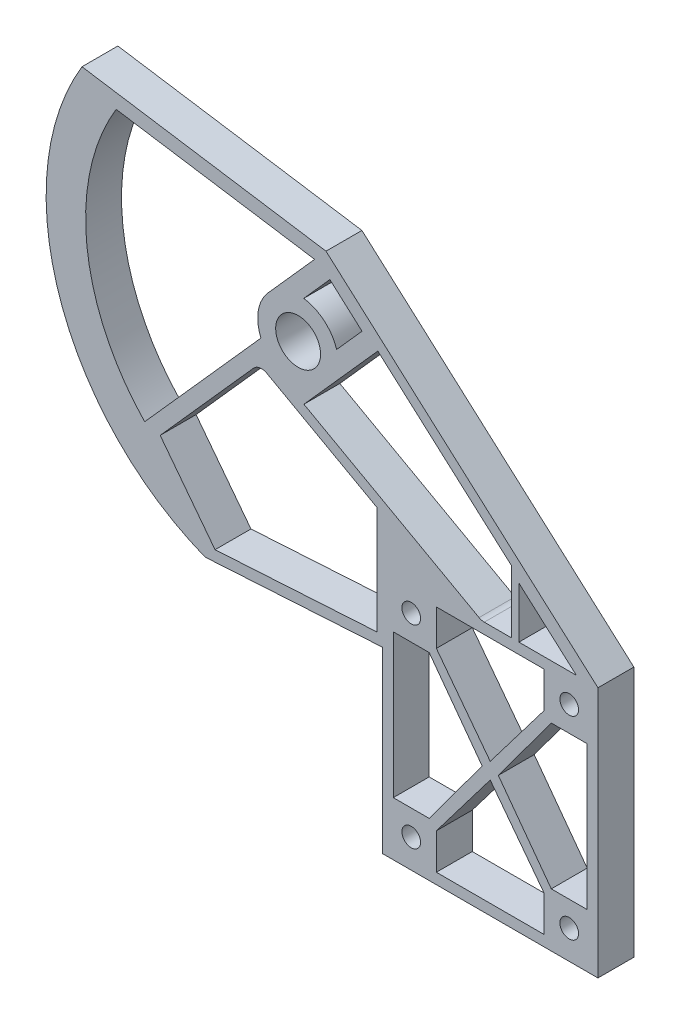
SolidWorks part; units mm, degrees
material "Magnesium Alloy"
ref_plane "Front Plane" through (0, 0, 0) normal (0, 0, 1) x (1, 0, 0)
ref_plane "Top Plane" through (0, 0, 0) normal (0, 1, 0) x (1, 0, 0)
ref_plane "Right Plane" through (0, 0, 0) normal (1, 0, 0) x (0, 0, -1)
sketch "Sketch1" plane through (0, 0, 0) normal (0, 0, 1) x (1, 0, 0)
  line L3 (22.6053, 67.0523) -> (98.8053, 67.0523)
  line L4 (98.8053, 155.9523) -> (98.8053, 67.0523)
  line L7 (60.7053, 155.2939) -> (60.7053, 67.0523) construction
  line L8 (184.9087, 111.5023) -> (-17.2677, 111.5023) construction
  line L11 (98.8053, 155.9523) -> (-49.1612, 287.7)
  line L14 (22.6053, 67.0523) -> (22.6053, 130.2741)
  line L15 (-40.152, 126.5029) -> (22.6053, 130.2741)
  arc A1 (-40.152, 126.5029) -> (-49.1612, 287.7) centre (-7.475, 209.1795) cw
  dimension "D3" = 88.9
  dimension "D1" = 88.9
  dimension "D7" = 44.45
  dimension "D8" = 38.1
  dimension "D9" = 76.2
extrude "Boss-Extrude1" add sketch "Sketch1" along normal blind 12.7
sketch "Sketch2" plane through (0, 0, 12.7) normal (0, 0, 1) x (1, 0, 0)
  line L2 (22.6053, 67.0523) -> (98.8053, 67.0523) construction
  line L3 (22.6053, 130.2741) -> (22.6053, 67.0523) construction
  circle A0 centre (-7.2397, 209.0383) radius 7.9375
  dimension "D2" = 15.875
  dimension "D1" = 141.986
  dimension "D3" = 29.845
extrude "Cut-Extrude1" cut sketch "Sketch2" against normal blind 25.4
ref_axis "Axis1" through (-7.2397, 209.0383, 0) along (0, 0, 1)
ref_axis "Axis2" through (-7.475, 209.1795, 12.7) along (0, 0, -1)
sketch "Sketch3" plane through (0, 0, 12.7) normal (0, 0, 1) x (1, 0, 0)
  line L0 (41.6553, 70.8623) -> (41.6553, 83.5623)
  line L1 (41.6553, 83.5623) -> (60.7053, 108.6448)
  line L2 (60.7053, 108.6448) -> (79.7553, 83.5623)
  line L3 (79.7553, 83.5623) -> (79.7553, 70.8623)
  line L4 (79.7553, 70.8623) -> (41.6553, 70.8623)
  line L5 (26.4153, 86.1023) -> (39.1153, 86.1023)
  line L6 (39.1153, 86.1023) -> (57.8478, 111.5023)
  line L7 (57.8478, 111.5023) -> (39.1153, 136.9023)
  line L8 (39.1153, 136.9023) -> (26.4153, 136.9023)
  line L9 (26.4153, 136.9023) -> (26.4153, 86.1023)
  line L10 (94.9953, 86.1023) -> (82.2953, 86.1023)
  line L11 (82.2953, 86.1023) -> (63.5628, 111.5023)
  line L12 (63.5628, 111.5023) -> (82.2953, 136.9023)
  line L13 (82.2953, 136.9023) -> (94.9953, 136.9023)
  line L14 (94.9953, 136.9023) -> (94.9953, 86.1023)
  line L15 (41.6553, 152.1423) -> (41.6553, 139.4423)
  line L16 (41.6553, 139.4423) -> (60.7053, 114.3598)
  line L17 (60.7053, 114.3598) -> (79.7553, 139.4423)
  line L18 (79.7553, 139.4423) -> (79.7553, 152.1423)
  line L19 (79.7553, 152.1423) -> (41.6553, 152.1423)
  line L20 (22.6053, 67.0523) -> (98.8053, 67.0523) construction
  line L21 (98.8053, 67.0523) -> (98.8053, 155.9523) construction
  line L22 (22.6053, 130.2741) -> (22.6053, 67.0523) construction
  dimension "D1" = 3.81
  dimension "D2" = 3.81
  dimension "D3" = 3.81
  dimension "D4" = 3.81
  dimension "D5" = 19.05
  dimension "D6" = 19.05
  dimension "D7" = 19.05
  dimension "D8" = 19.05
  dimension "D10" = 19.05
  dimension "D11" = 12.7
  dimension "D12" = 12.7
  dimension "D13" = 12.7
  dimension "D14" = 12.7
  dimension "D16" = 5.715
  dimension "D17" = 5.715
extrude "Cut-Extrude2" cut sketch "Sketch3" against normal blind 15.24
sketch "Sketch5" plane through (0, 0, 12.7) normal (0, 0, 1) x (1, 0, 0)
  line L2 (-0.7594, 237.8017) -> (-42.8182, 275.2504)
  line L3 (98.8053, 155.9523) -> (-49.1612, 287.7) construction
  line L4 (-36.6202, 130.532) -> (-56.0379, 155.8518)
  line L5 (-17.9104, 218.5393) -> (-0.7594, 237.8017)
  line L6 (-5.268, 223.1891) -> (3.9831, 233.579)
  line L7 (3.9831, 233.579) -> (15.3651, 223.4446)
  line L8 (15.3651, 223.4446) -> (6.3804, 213.3538)
  line L12 (-61.5192, 157.2784) -> (-20.3953, 203.4649)
  line L14 (20.7003, 172.0765) -> (-20.9942, 195.2095)
  line L15 (-20.9942, 195.2095) -> (-56.0379, 155.8518)
  line L17 (26.4153, 136.9023) -> (26.4153, 86.1023) construction
  line L18 (-36.6202, 130.532) -> (20.7003, 133.9765)
  line L19 (20.7003, 133.9765) -> (20.7003, 172.0765)
  line L20 (-40.152, 126.5029) -> (22.6053, 130.2741) construction
  arc A0 (-61.5192, 157.2784) -> (-42.8182, 275.2504) centre (-7.475, 209.1795) cw
  arc A1 (-49.1612, 287.7) -> (-40.152, 126.5029) centre (-7.475, 209.1795) ccw construction
  arc A2 (-20.3953, 203.4649) -> (-17.9104, 218.5393) centre (-7.2397, 209.0383) cw
  circle A3 centre (-7.2397, 209.0383) radius 7.9375 construction
  arc A4 (-5.268, 223.1891) -> (6.3804, 213.3538) centre (-7.2397, 209.0383) cw
  dimension "D1" = 13.97
  dimension "D4" = 6.35
  dimension "D6" = 6.35
  dimension "D2" = 5.08
  dimension "D3" = 90
  dimension "D5" = 6.35
  dimension "D7" = 15.24
  dimension "D8" = 5.08
  dimension "D9" = 38.1
  dimension "D10" = 13.97
  dimension "D12" = 5.715
  dimension "D13" = 3.81
extrude "Cut-Extrude4" cut sketch "Sketch5" against normal blind 12.7 contours A2 L5 L2 A0 | L15 L4 L18 L19 L14 | L12 A2 L5 L2 A0 | L8 A4 L6 L7 region at (-48.435, 220.0414, 12.7)
sketch "Sketch4" plane through (0, 0, 12.7) normal (0, 0, 1) x (1, 0, 0)
  line L3 (57.6155, 155.9523) -> (-5.1971, 190.802)
  line L4 (-5.1971, 190.802) -> (20.9522, 220.1704)
  line L15 (20.7003, 172.0765) -> (-20.9942, 195.2095) construction
  line L16 (15.3651, 223.4446) -> (6.3804, 213.3538) construction
  line L18 (91.166, 155.9523) -> (70.846, 155.9523)
  line L19 (70.846, 155.9523) -> (70.846, 174.045)
  line L20 (70.846, 174.045) -> (91.166, 155.9523)
  line L21 (98.8053, 155.9523) -> (-49.1612, 287.7) construction
  line L22 (79.7553, 152.1423) -> (41.6553, 152.1423) construction
  line L23 (68.306, 155.9523) -> (68.306, 178.007)
  line L24 (68.306, 178.007) -> (20.9522, 220.1704)
  line L26 (57.6155, 155.9523) -> (68.306, 155.9523)
  dimension "D1" = 3.81
  dimension "D2" = 5.08
  dimension "D3" = 20.32
  dimension "D4" = 3.81
  dimension "D5" = 2.54
  dimension "D6" = 6.35
  dimension "D8" = 3.81
extrude "Cut-Extrude3" cut sketch "Sketch4" against normal blind 12.7
sketch "Sketch6" plane through (0, 0, 12.7) normal (0, 0, 1) x (1, 0, 0)
  line L0 (-45.205, 275.6751) -> (-52.1749, 281.881)
  line L1 (-80.3549, 164.771) -> (-74.1405, 171.7505)
  line L3 (98.8053, 155.9523) -> (-49.1612, 287.7) construction
  line L4 (-61.5192, 157.2784) -> (-20.3953, 203.4649) construction
  arc A0 (-45.205, 275.6751) -> (-74.1405, 171.7505) centre (-7.475, 209.1795) ccw
  arc A1 (-52.1749, 281.881) -> (-80.3549, 164.771) centre (-7.475, 209.1795) ccw
  dimension "D1" = 8.89
  dimension "D2" = 76.454
  dimension "D3" = 6.35
  dimension "D4" = 19.05
extrude "Cut-Extrude5" [suppressed] cut sketch "Sketch6" against normal blind 3.81
fillet "Fillet4" radius 3.81 2 edges at (-20.9942, 195.2095, 6.35) (57.6155, 155.9523, 6.35)
sketch "Sketch10" plane through (0, 0, 12.7) normal (0, 0, 1) x (1, 0, 0)
  line L0 (22.6053, 67.0523) -> (98.8053, 67.0523) construction
  line L1 (98.8053, 67.0523) -> (98.8053, 155.9523) construction
  line L2 (22.6053, 130.2741) -> (22.6053, 67.0523) construction
  circle A0 centre (32.7653, 77.2123) radius 3.302
  circle A1 centre (32.7653, 145.7923) radius 3.302
  circle A2 centre (88.6453, 145.7923) radius 3.302
  circle A3 centre (88.6453, 77.2123) radius 3.302
  dimension "D1" = 6.604
  dimension "D2" = 10.16
  dimension "D3" = 10.16
  dimension "D4" = 10.16
  dimension "D5" = 10.16
extrude "Cut-Extrude8" cut sketch "Sketch10" against normal up to next
sketch "Sketch11" plane through (0, 0, 12.7) normal (0, 0, 1) x (1, 0, 0)
  line L0 (-78.7242, 164.6859) -> (-71.3414, 157.7059)
  line L1 (-71.3414, 157.7059) -> (-86.3104, 140.8941)
  line L2 (-86.3104, 140.8941) -> (-66.8677, 134.9879)
  line L5 (-61.5192, 157.2784) -> (-20.3953, 203.4649) construction
  arc A0 (-42.8182, 275.2504) -> (-61.5192, 157.2784) centre (-7.475, 209.1795) ccw construction
  arc A3 (-78.7242, 164.6859) -> (-84.8667, 165.4333) centre (-76.7166, 206.8048) cw
  arc A4 (-49.1612, 287.7) -> (-40.152, 126.5029) centre (-7.475, 209.1795) ccw construction
  arc A5 (-84.8667, 165.4333) -> (-66.8677, 134.9879) centre (-43.4397, 169.3814) ccw
  dimension "D1" = 10.16
  dimension "D2" = 81.28
  dimension "D3" = 7.62
  dimension "D4" = 20.32
  dimension "D5" = 15.24
extrude "Cut-Extrude9" [suppressed] cut sketch "Sketch11" against normal blind 12.7
fillet "Fillet6" [suppressed] radius 3.81
sketch "Sketch13" [suppressed] plane through (0, 0, 12.7) normal (0, 0, 1) x (1, 0, 0)
  line L0 (98.8053, 155.9523) -> (-49.1612, 287.7) construction
  line L1 (-50.3104, 281.9213) -> (-42.8182, 275.2504)
  line L2 (-42.8182, 275.2504) -> (-55.8246, 151.936)
  line L3 (-55.8246, 151.936) -> (-61.138, 143.7544)
  arc A0 (-50.3104, 281.9213) -> (-61.138, 143.7544) centre (-7.2397, 209.0383) ccw
  arc A1 (-42.8182, 275.2504) -> (-35.7205, 139.7771) centre (-7.475, 209.1795) ccw construction
  arc A2 (-42.8182, 275.2504) -> (-35.7205, 139.7771) centre (-7.475, 209.1795) ccw construction
  dimension "D3" = 84.6582
  dimension "D1" = 5.08
  dimension "D2" = 7.62
  dimension "D4" = 23.495
extrude "Cut-Extrude10" [suppressed] cut sketch "Sketch13" against normal blind 15.24
fillet "Fillet8" [suppressed] radius 2.54
fillet "Fillet9" [suppressed] radius 3.81
sketch "Sketch14" plane through (0, 0, 12.7) normal (0, 0, 1) x (1, 0, 0)
  line L0 (-0.7594, 237.8017) -> (-90.2849, 256.2973)
  line L1 (-90.2849, 256.2973) -> (-56.5034, 294.2374)
  line L2 (-56.5034, 294.2374) -> (2.6187, 241.5957)
  line L3 (2.6187, 241.5957) -> (-0.7594, 237.8017)
  line L4 (98.8053, 155.9523) -> (-49.1612, 287.7) construction
  dimension "D1" = 50.8
extrude "Cut-Extrude11" cut sketch "Sketch14" against normal blind 12.7
sketch "Sketch15" plane through (0, 0, 12.7) normal (0, 0, 1) x (1, 0, 0)
  line L0 (2.6187, 241.5957) -> (-83.6954, 254.9359)
  line L1 (-83.6954, 254.9359) -> (-84.4714, 249.9156)
  line L2 (-84.4714, 249.9156) -> (-1.4045, 237.0772)
  line L3 (-17.9104, 218.5393) -> (2.6187, 241.5957) construction
  line L4 (-1.4045, 237.0772) -> (2.6187, 241.5957)
  dimension "D1" = 5.08
extrude "Boss-Extrude2" add sketch "Sketch15" against normal blind 12.7
sketch "Sketch16" [suppressed] plane through (0, 0, 12.7) normal (0, 0, 1) x (1, 0, 0)
  circle A0 centre (-81.6167, 249.4744) radius 5.08
  circle A1 centre (-81.6167, 249.4744) radius 2.54
  dimension "D1" = 10.16
extrude "Boss-Extrude3" [suppressed] add sketch "Sketch16" against normal blind 12.7
sketch "Sketch17" [suppressed] plane through (0, 0, 12.7) normal (0, 0, 1) x (1, 0, 0)
  circle A0 centre (-81.6167, 249.4744) radius 2.54
extrude "Cut-Extrude12" [suppressed] cut sketch "Sketch17" against normal blind 12.7
sketch "Sketch18" [suppressed] plane through (0, 0, 12.7) normal (0, 0, 1) x (1, 0, 0)
  line L0 (-76.5963, 248.6984) -> (1.9776, 219.9549)
  line L1 (1.9776, 219.9549) -> (91.166, 155.9523)
  line L2 (91.166, 155.9523) -> (97.7253, 155.9523)
  line L3 (97.7253, 155.9523) -> (11.1826, 258.9905)
  line L4 (11.1826, 258.9905) -> (-76.5963, 256.9042)
  line L5 (-76.5963, 256.9042) -> (-76.5963, 248.6984)
  arc A0 (6.3804, 213.3538) -> (-5.268, 223.1891) centre (-7.2397, 209.0383) ccw construction
extrude "Cut-Extrude13" [suppressed] cut sketch "Sketch18" against normal blind 12.7
sketch "Sketch21" plane through (0, 0, 12.7) normal (0, 0, 1) x (1, 0, 0)
  line L0 (91.166, 155.9523) -> (6.3804, 213.3538)
  line L2 (70.846, 155.9523) -> (91.166, 155.9523) construction
  line L3 (91.166, 155.9523) -> (70.846, 174.045) construction
  line L4 (91.166, 155.9523) -> (98.8053, 155.9523)
  line L5 (-16.0672, 197.804) -> (-59.6965, 117.8218)
  line L6 (-59.6965, 117.8218) -> (-158.5524, 218.788)
  line L7 (-158.5524, 218.788) -> (-79.0512, 290.8068)
  line L8 (-79.0512, 290.8068) -> (114.09, 194.9377)
  line L9 (114.09, 194.9377) -> (98.8053, 155.9523)
  arc A2 (6.3804, 213.3538) -> (-16.0672, 197.804) centre (-7.2397, 209.0383) ccw
